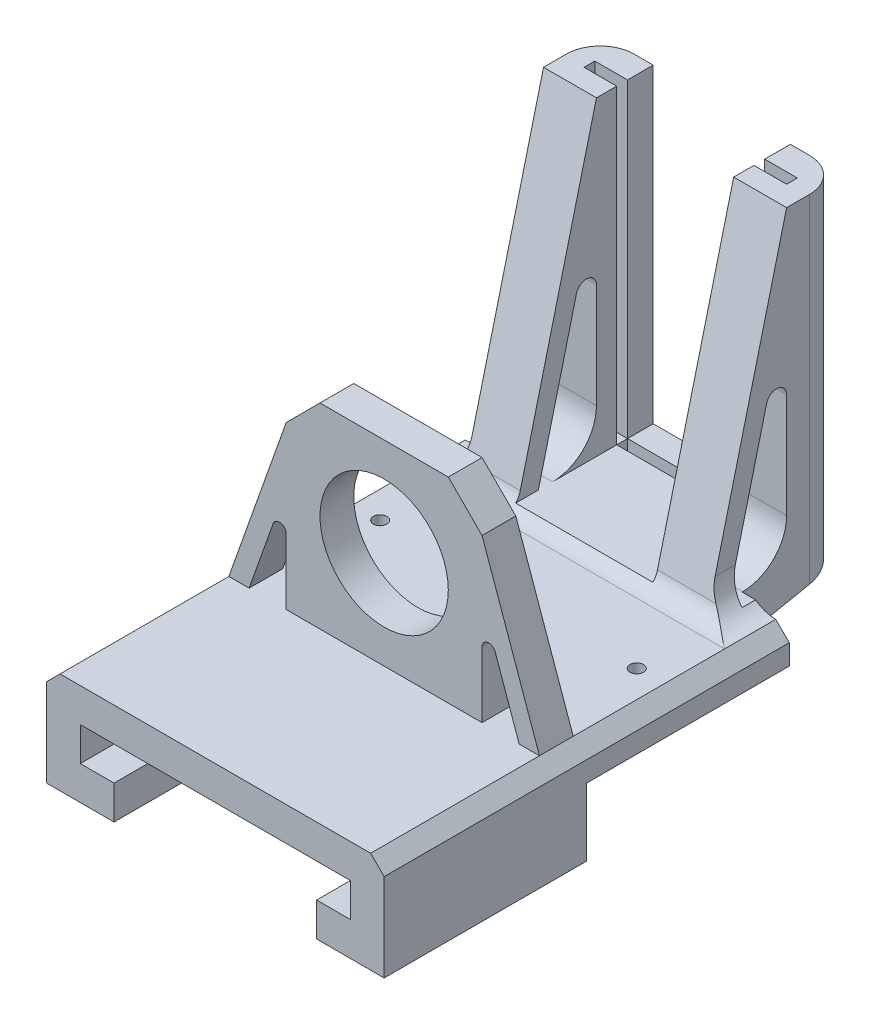
SolidWorks part; units mm, degrees
material "9400A光敏树脂"
ref_plane "前视基准面" through (0, 0, 0) normal (0, 0, 1) x (1, 0, 0)
ref_plane "上视基准面" through (0, 0, 0) normal (0, 1, 0) x (1, 0, 0)
ref_plane "右视基准面" through (0, 0, 0) normal (1, 0, 0) x (0, 0, -1)
other "Configuration Table"
sketch "草图2" plane through (0, 0, 0) normal (0, 1, 0) x (1, 0, 0)
  line L1 (-30, 30) -> (30, 30)
  line L2 (-30, 30) -> (-30, -30)
  line L3 (-30, -30) -> (30, -30)
  line L4 (30, 30) -> (30, -30)
  line L5 (-30, 30) -> (30, -30) construction
  line L6 (-30, -30) -> (30, 30) construction
  point P0 (0, 0)
  dimension "D1" = 60
  dimension "D2" = 60
extrude "凸台-拉伸1" add sketch "草图2" along normal blind 3
sketch "草图7" plane through (0, 0, 0) normal (0, 0, 1) x (1, 0, 0)
  line L0 (0, -1000) -> (0, 49000) construction
  line L1 (-25, 0) -> (-25, -10)
  line L2 (-30, 0) -> (30, 0) construction
  line L3 (-25, -10) -> (-15, -10)
  line L4 (-15, -10) -> (-15, -5)
  line L5 (-15, -5) -> (-20, -5)
  line L6 (-20, -5) -> (-20, 0)
  line L7 (-20, 0) -> (-25, 0)
  line L8 (-30, 3) -> (-30, 0) construction
  line L9 (20, 0) -> (25, 0)
  line L10 (20, -5) -> (20, 0)
  line L11 (15, -5) -> (20, -5)
  line L12 (15, -10) -> (15, -5)
  line L13 (25, -10) -> (15, -10)
  line L14 (25, 0) -> (25, -10)
  dimension "D1" = 5
  dimension "D2" = 5
  dimension "D3" = 10
  dimension "D4" = 5
  dimension "D5" = 5
extrude "凸台-拉伸3" add sketch "草图7" against normal blind 30 from surface at 30 starting at face at (0, 1.5, 30)
sketch "草图8" plane through (0, 0, 0) normal (0, 1, 0) x (1, 0, 0)
  line L0 (0, -1000) -> (0, 49000) construction
  line L1 (-18, 25) -> (18, 25)
  line L2 (18, 25) -> (18, 45)
  line L3 (18, 45) -> (-18, 45)
  line L4 (-18, 45) -> (-18, 25)
  line L5 (30, 30) -> (-30, 30) construction
  point P7 (0, 25)
  dimension "D1" = 36
  dimension "D2" = 20
  dimension "D3" = 5
extrude "凸台-拉伸4" add sketch "草图8" along normal blind 3 from surface at 3 starting at face at (0, 3, 0)
sketch "草图10" plane through (0, 0, 0) normal (0, 1, 0) x (1, 0, 0)
  line L0 (-18, 45) -> (18, 45) construction
  line L1 (-10.16, 41.2) -> (10.16, 41.2)
  line L2 (-10.16, 41.2) -> (-10.16, 39.6)
  line L3 (-10.16, 39.6) -> (10.16, 39.6)
  line L4 (10.16, 41.2) -> (10.16, 39.6)
  point P6 (0, 45)
  point P7 (0, 41.2)
  dimension "D1" = 3.8
  dimension "D2" = 1.6
  dimension "D3" = 20.32
extrude "切除-拉伸2" cut sketch "草图10" against normal up to surface (3 mm away) from surface at 6 up to face at (0, 3, -37.5) starting at face at (0, 6, -35)
sketch "草图11" plane through (0, 0, 0) normal (0, 1, 0) x (1, 0, 0)
  line L0 (0, -1000) -> (0, 49000) construction
  line L1 (18, 41.2) -> (15, 41.2) construction
  line L2 (18, 45) -> (18, 25) construction
  line L3 (10.16, 41.2) -> (-10.16, 41.2) construction
  line L4 (10.16, 41.2) -> (10.16, 45)
  line L5 (-18, 45) -> (18, 45) construction
  line L6 (10.16, 45) -> (18, 45)
  line L7 (15, 39.6) -> (18, 39.6) construction
  line L8 (-10.16, 39.6) -> (10.16, 39.6) construction
  line L9 (18, 45) -> (18, 36.6)
  line L10 (18, 36.6) -> (10.16, 36.6)
  line L11 (10.16, 36.6) -> (10.16, 39.6)
  line L12 (10.16, 39.6) -> (15, 39.6)
  line L13 (10.16, 41.2) -> (15, 41.2)
  line L14 (15, 41.2) -> (15, 39.6)
  line L15 (-15, 39.6) -> (-18, 39.6) construction
  line L16 (-18, 41.2) -> (-15, 41.2) construction
  line L17 (-15, 41.2) -> (-15, 39.6)
  line L18 (-10.16, 41.2) -> (-15, 41.2)
  line L19 (-10.16, 39.6) -> (-15, 39.6)
  line L20 (-10.16, 36.6) -> (-10.16, 39.6)
  line L21 (-18, 36.6) -> (-10.16, 36.6)
  line L22 (-18, 45) -> (-18, 36.6)
  line L23 (-10.16, 45) -> (-18, 45)
  line L24 (-10.16, 41.2) -> (-10.16, 45)
  dimension "D1" = 3
  dimension "D2" = 3
  dimension "D3" = 3
extrude "凸台-拉伸5" add sketch "草图11" along normal blind 46 from surface at 6 starting at face at (0, 6, -40.4)
sketch "草图12" plane through (0, 0, 0) normal (1, 0, 0) x (0, 0, -1)
  line L0 (30, 0) -> (35, 3)
  line L1 (45, 3) -> (30, 3) construction
  line L2 (35, 3) -> (30, 3)
  line L3 (30, 3) -> (30, 0) construction
  line L4 (30, 3) -> (30, 0)
  dimension "D1" = 5
extrude "凸台-拉伸6" add sketch "草图12" along normal up to surface (36 mm away) from surface at -18 up to face at (18, 17.8571, -34.7429) starting at face at (-18, 17.8571, -34.7429)
sketch "草图13" plane through (0, 0, 0) normal (1, 0, 0) x (0, 0, -1)
  line L0 (25, 6) -> (36.6, 52)
  line L1 (25, 6) -> (28, 6)
  line L2 (36.6, 40.1034) -> (36.6, 52)
  line L3 (28, 6) -> (36.6, 40.1034)
  dimension "D1" = 3
extrude "凸台-拉伸8" add sketch "草图13" against normal up to surface (7.84 mm away) from surface at 18 up to face at (10.16, 29, -43.1) starting at face at (18, 14.2222, -34.2444)
sketch "草图14" plane through (0, 0, 0) normal (1, 0, 0) x (0, 0, -1)
  line L4 (36.6, 52) -> (25, 6)
  line L5 (36.6, 40.1034) -> (36.6, 52)
  line L6 (28, 6) -> (36.6, 40.1034)
  line L7 (25, 6) -> (28, 6)
  line L8 (36.6, 52) -> (25, 6)
  line L9 (36.6, 40.1034) -> (36.6, 52)
  line L10 (28, 6) -> (36.6, 40.1034)
  line L11 (25, 6) -> (28, 6)
  dimension "D1" = 0
extrude "凸台-拉伸9" add sketch "草图14" against normal up to surface (7.84 mm away) from surface at -10.16 up to face at (-18, 14.2222, -34.2444) starting at face at (-10.16, 29, -43.1)
sketch "草图15" plane through (0, 0, 0) normal (1, 0, 0) x (0, 0, -1)
  line L0 (25, 3) -> (24.2435, 3)
  line L1 (-30, 3) -> (30, 3) construction
  line L2 (24.2435, 3) -> (25, 6)
  line L3 (25, 6) -> (25, 3)
  line L4 (25, 6) -> (36.6, 52) construction
extrude "凸台-拉伸10" add sketch "草图15" against normal up to surface (36 mm away) from surface
sketch "草图16" plane through (0, 0, 0) normal (0, 1, 0) x (1, 0, 0)
  line L1 (25, -30) -> (30, -30)
  line L2 (25, -30) -> (25, 30)
  line L3 (25, 30) -> (30, 30)
  line L4 (30, -30) -> (30, 30)
  line L5 (-25, -30) -> (-30, -30)
  line L6 (-25, -30) -> (-25, 30)
  line L7 (-25, 30) -> (-30, 30)
  line L8 (-30, -30) -> (-30, 30)
extrude "切除-拉伸3" cut sketch "草图16" along normal up to surface (3 mm away) from surface at 0 up to face at (0, 3, -13.5609) starting at face at (0, 0, 4.2857)
sketch "草图17" plane through (0, 0, 0) normal (1, 0, 0) x (0, 0, -1)
  line L0 (30, 0) -> (45, 3)
  line L1 (45, 3) -> (30, 3)
  line L2 (30, 3) -> (30, 0)
extrude "凸台-拉伸11" add sketch "草图17" against normal blind 4 from surface at 18 starting at face at (18, 16.5714, -35.1205)
sketch "草图18" plane through (0, 0, 0) normal (1, 0, 0) x (0, 0, -1)
  line L0 (30, 0) -> (30, 3)
  line L1 (30, 3) -> (45, 3)
  line L2 (45, 3) -> (30, 0)
extrude "凸台-拉伸12" add sketch "草图18" along normal blind 4 from surface at -18 starting at face at (-18, 17.3678, -33.7333)
fillet "圆角3" radius 5 2 edges at (-18, 27.5, -45) (18, 27.5, -45)
fillet "圆角4" radius 10 1 edges at (0, 3, -35)
sketch "草图22" plane through (0, 0, 0) normal (0, 0, 1) x (1, 0, 0)
  line L1 (25, 3) -> (-25, 3)
  line L2 (25, 3) -> (25, 5)
  line L3 (25, 5) -> (-25, 5)
  line L4 (-25, 3) -> (-25, 5)
  dimension "D1" = 50
  dimension "D2" = 2
extrude "凸台-拉伸14" add sketch "草图22" against normal up to surface (60 mm away) from surface at 30 up to face at (-21.5, 1.5, -30) starting at face at (0, -4.5, 30)
sketch "草图24" plane through (0, 0, 0) normal (0, 0, 1) x (1, 0, 0)
  line L0 (-25, 5) -> (-23, 5)
  line L1 (25, 5) -> (-25, 5) construction
  line L2 (-23, 5) -> (-25, 3)
  line L3 (-25, 5) -> (-25, -10) construction
  line L4 (-25, 3) -> (-25, 5)
  line L5 (25, 5) -> (25, 3)
  line L6 (25, -10) -> (25, 5) construction
  line L7 (25, 3) -> (23, 5)
  line L8 (23, 5) -> (25, 5)
  dimension "D1" = 2
  dimension "D2" = 2
  dimension "D3" = 2
  dimension "D4" = 2
extrude "切除-拉伸4" cut sketch "草图24" against normal up to surface (60 mm away) from surface at 30 up to face at (-21.5, 2.5, -30) starting at face at (0, -4.1667, 30)
sketch "草图26" plane through (0, 0, 0) normal (0, 1, 0) x (1, 0, 0)
  circle A0 centre (0, 0) radius 12.5
  dimension "D1" = 25
extrude "切除-拉伸6" cut sketch "草图26" along normal blind 2 from surface at 0 starting at face at (0, 0, -10)
fillet "圆角5" radius 3 1 edges at (0, 0, 12.5)
fillet "圆角7" radius 5 2 edges at (-18, 5, -27.3739) (18, 5, -27.3739)
fillet "圆角8" radius 6.5 2 edges at (14.08, 6, -36.6) (-14.08, 6, -36.6)
fillet "圆角9" radius 1.5 2 edges at (-14.08, 40.1034, -36.6) (14.08, 40.1034, -36.6)
fillet "圆角10" radius 3 1 edges at (0, 5, -24.7478)
sketch "草图27" plane through (0, 0, 0) normal (0, 1, 0) x (1, 0, 0)
  line L1 (-14.5, 0) -> (14.5, 0)
  line L2 (-14.5, 0) -> (-14.5, -5)
  line L3 (-14.5, -5) -> (14.5, -5)
  line L4 (14.5, 0) -> (14.5, -5)
  point P4 (0, 0)
  dimension "D1" = 29
  dimension "D2" = 5
extrude "凸台-拉伸15" add sketch "草图27" along normal blind 29 from surface at 5 starting at face at (0, 5, 3.7948)
sketch "草图28" plane through (0, 0, 0) normal (0, 0, 1) x (1, 0, 0)
  line L0 (14.5, 34) -> (-14.5, 5) construction
  circle A0 centre (0, 19.5) radius 9.5
  dimension "D1" = 19
extrude "切除-拉伸7" cut sketch "草图28" against normal up to surface (5 mm away) from surface at 5 up to face at (0, 19.5, 0) starting at face at (0, 19.5, 5)
sketch "草图29" plane through (0, 0, 0) normal (0, 0, 1) x (1, 0, 0)
  line L0 (-14.5, 34) -> (-9.5, 34)
  line L1 (14.5, 34) -> (-14.5, 34) construction
  line L2 (-9.5, 34) -> (-14.5, 29)
  line L3 (-14.5, 34) -> (-14.5, 5) construction
  line L4 (-14.5, 29) -> (-14.5, 34)
  line L5 (14.5, 34) -> (9.5, 34)
  line L6 (9.5, 34) -> (14.5, 29)
  line L7 (14.5, 34) -> (14.5, 5) construction
  line L8 (14.5, 29) -> (14.5, 34)
  dimension "D1" = 5
  dimension "D2" = 5
  dimension "D3" = 5
  dimension "D4" = 5
extrude "切除-拉伸8" cut sketch "草图29" against normal up to surface (5 mm away) from surface at 5 up to face at (-9.5, 19.5, 0) starting at face at (9.5, 19.5, 5)
sketch "草图30" plane through (0, 0, 0) normal (0, 0, 1) x (1, 0, 0)
  line L0 (-23, 5) -> (-14.5, 29)
  line L1 (-14.5, 29) -> (-14.5, 20.5294)
  line L2 (-14.5, 29) -> (-14.5, 5) construction
  line L3 (-14.5, 20.5294) -> (-20, 5)
  line L4 (23, 5) -> (-23, 5) construction
  line L5 (-20, 5) -> (-23, 5)
  line L6 (0, -1000) -> (0, 49000) construction
  line L7 (20, 5) -> (23, 5)
  line L8 (14.5, 20.5294) -> (20, 5)
  line L9 (14.5, 29) -> (14.5, 20.5294)
  line L10 (23, 5) -> (14.5, 29)
  dimension "D1" = 3
extrude "凸台-拉伸16" add sketch "草图30" against normal up to surface (5 mm away) from surface
fillet "圆角11" radius 1 2 edges at (14.5, 20.5294, 2.5) (-14.5, 20.5294, 2.5)
sketch "草图31" plane through (0, 0, 0) normal (0, 1, 0) x (1, 0, 0)
  line L0 (-19, 13.4104) -> (19, 13.4104) construction
  line L1 (23, 22.4104) -> (-23, 22.4104) construction
  circle A0 centre (-19, 13.4104) radius 1
  circle A1 centre (19, 13.4104) radius 1
  point P3 (0, 13.4104)
  dimension "D3" = 2
  dimension "D4" = 2
  dimension "D1" = 38
  dimension "D2" = 9
extrude "切除-拉伸9" cut sketch "草图31" against normal up to surface (5 mm away) from surface at 5 up to face at (0, 0, 15.3284) starting at face at (0, 5, 2.9316)
sketch "草图32" plane through (0, 0, 0) normal (0, 1, 0) x (1, 0, 0)
  circle A0 centre (19, 13.4104) radius 1.75
  circle A1 centre (-19, 13.4104) radius 1.75
  dimension "D1" = 3.5
  dimension "D2" = 3.5
extrude "切除-拉伸10" cut sketch "草图32" along normal blind 2 from surface at 0 starting at face at (19, 0, -12.4104)
